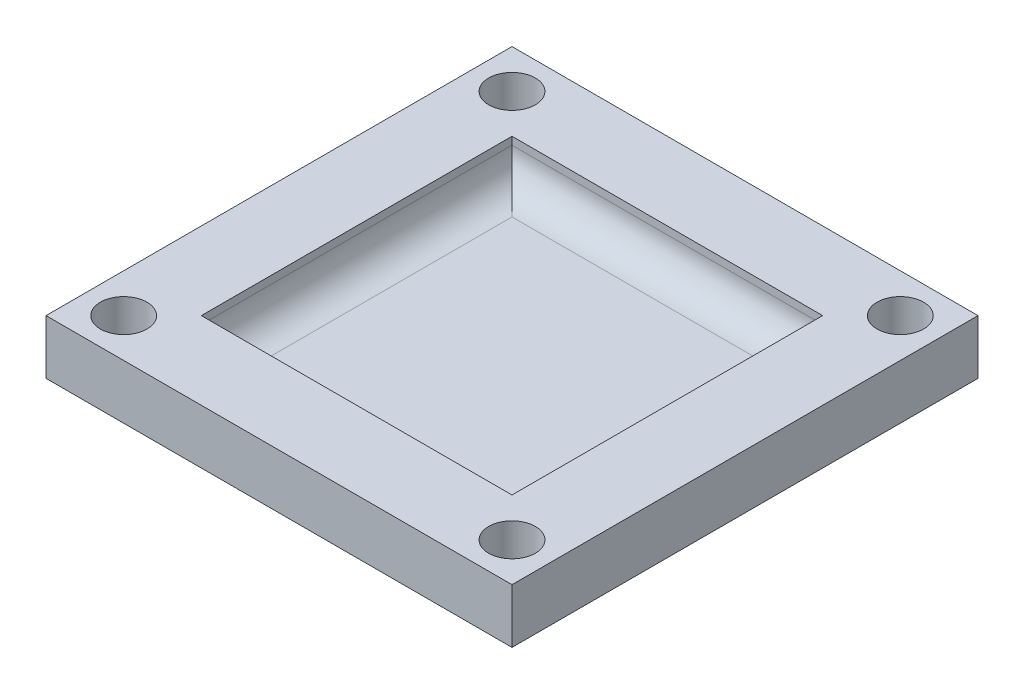
SolidWorks part; units mm, degrees
ref_plane "Front Plane" through (0, 0, 0) normal (0, 0, 1) x (1, 0, 0)
ref_plane "Top Plane" through (0, 0, 0) normal (0, 1, 0) x (1, 0, 0)
ref_plane "Right Plane" through (0, 0, 0) normal (1, 0, 0) x (0, 0, -1)
sketch "Sketch2" plane through (0, 0, 0) normal (0, 1, 0) x (1, 0, 0)
  line L5 (-15, -15) -> (15, -15)
  line L6 (-15, -15) -> (-15, 15)
  line L7 (-15, 15) -> (15, 15)
  line L8 (15, -15) -> (15, 15)
  line L9 (-15, -15) -> (15, 15) construction
  line L10 (-15, 15) -> (15, -15) construction
  line L11 (-10, -10) -> (10, -10)
  line L12 (-10, -10) -> (-10, 10)
  line L13 (-10, 10) -> (10, 10)
  line L14 (10, -10) -> (10, 10)
  line L15 (-10, -10) -> (10, 10) construction
  line L16 (-10, 10) -> (10, -10) construction
  point P0 (0, 0)
  point P6 (0, 0)
  dimension "D1" = 30
  dimension "D2" = 30
  dimension "D3" = 20
  dimension "D4" = 20
extrude "Boss-Extrude2" add sketch "Sketch2" along normal blind 3.5 from surface starting at plane "Top Plane"
extrude "Boss-Extrude3" add sketch "Sketch2<4>" along normal blind 1 contours L13 L14 L11 L12
sketch "Sketch2<4>" plane through (0, 0, 0) normal (0, 1, 0) x (1, 0, 0) same geometry as "Sketch2"
fillet "Fillet1" radius 2 4 edges at (10, 1, 0) (0, 1, 10) (0, 1, -10) (-10, 1, 0)
sketch "Sketch6" plane through (0, 3.5, 0) normal (0, 1, 0) x (1, 0, 0)
  line L0 (-10, 10) -> (-15, 15)
  line L1 (10, 10) -> (15, 15)
  line L2 (10, -10) -> (15, -15)
  line L3 (-10, -10) -> (-15, -15)
  circle A0 centre (-12.5, 12.5) radius 1.5
  circle A1 centre (12.5, 12.5) radius 1.5
  circle A2 centre (12.5, -12.5) radius 1.5
  circle A3 centre (-12.5, -12.5) radius 1.5
extrude "Cut-Extrude1" cut sketch "Sketch6" against normal blind 4 contours L0 A0 | L0 A0 | L1 A1 | L1 A1 | L2 A2 | L2 A2 | L3 A3 | L3 A3 region at (-12.9502, 3.5, -12.0498) region at (-12.0498, 3.5, -12.9502) region at (12.0498, 3.5, -12.9502) region at (12.9502, 3.5, -12.0498) region at (12.9502, 3.5, 12.0498) region at (12.0498, 3.5, 12.9502) region at (-12.0498, 3.5, 12.9502) region at (-12.9502, 3.5, 12.0498)
